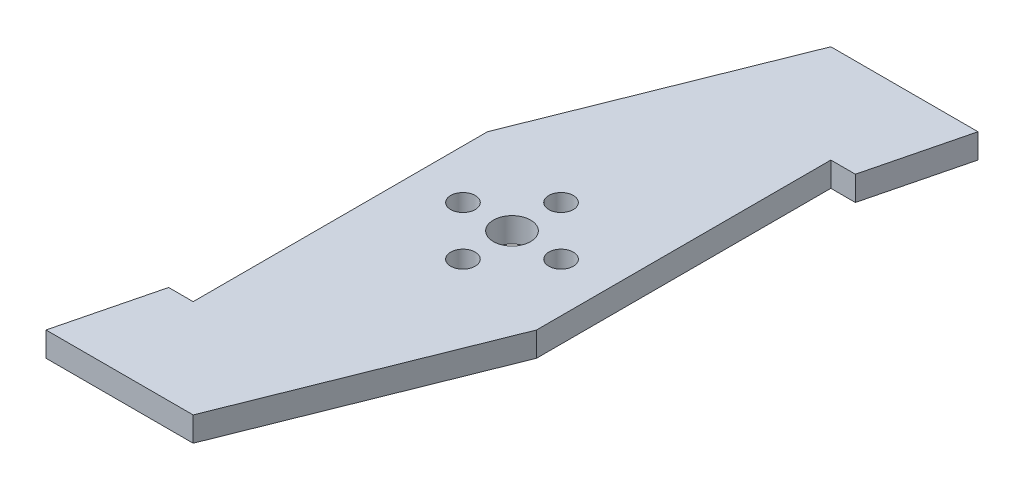
SolidWorks part; units mm, degrees
material "AISI Type A2 Tool Steel"
ref_plane "Front Plane" through (0, 0, 0) normal (0, 0, 1) x (1, 0, 0)
ref_plane "Top Plane" through (0, 0, 0) normal (0, 1, 0) x (1, 0, 0)
ref_plane "Right Plane" through (0, 0, 0) normal (1, 0, 0) x (0, 0, -1)
sketch "Sketch2" plane through (0, 0, 0) normal (0, 1, 0) x (1, 0, 0)
  line L14 (25.4, -82.55) -> (-25.4, -82.55)
  line L16 (25.4, -82.55) -> (25.4, 82.55)
  line L17 (-25.4, -82.55) -> (-25.4, 82.55)
  line L18 (25.4, 82.55) -> (-25.4, 82.55)
  line L19 (25.4, -82.55) -> (-25.4, 82.55) construction
  line L20 (-25.4, -82.55) -> (25.4, 82.55) construction
  circle A4 centre (0, 0) radius 82.55 construction
  arc A5 (-82.55, 0) -> (82.55, 0) centre (0, 0) cw
  dimension "D1" = 165.1
  dimension "D2" = 165.1
  dimension "D3" = 50.8
extrude "Boss-Extrude2" add sketch "Sketch2" along normal mid plane 6.35 contours A5 L17 L14 L16 | L18 L17 L14 L16 region at (0, 0, 0.6565)
sketch "Sketch6" plane through (0, 3.175, 0) normal (0, 1, 0) x (1, 0, 0)
  line L2 (31.75, 57.15) -> (25.4, 57.15)
  line L3 (25.4, 82.55) -> (25.4, 57.15)
  line L4 (-25.4, -82.55) -> (-38.1, -82.55)
  line L9 (-31.75, -57.15) -> (-38.1, -82.55)
  line L10 (-31.75, -57.15) -> (-25.4, -57.15)
  line L11 (-25.4, -82.55) -> (-25.4, -57.15)
  line L12 (25.4, -82.55) -> (-25.4, -82.55) construction
  line L13 (31.75, 57.15) -> (38.1, 82.55)
  line L15 (25.4, 82.55) -> (38.1, 82.55)
  point P10 (0, 0)
  point P13 (0, 0)
  point P14 (0, 0)
  dimension "D1" = 25.4
  dimension "D2" = 6.35
  dimension "D4" = 12.7
  dimension "D3" = 2
extrude "Boss-Extrude3" add sketch "Sketch6" against normal up to surface (6.35 mm away) contours L4 L9 L10 L11 | L15 L13 L2 L3 up to face at (0, -3.175, 0)
sketch "Sketch3" plane through (0, 3.175, 0) normal (0, 1, 0) x (1, 0, 0)
  circle A2 centre (0, 0) radius 4.826
  dimension "D1" = 9.652
extrude "Cut-Extrude1" cut sketch "Sketch3" against normal through all
sketch "Sketch4" plane through (0, 3.175, 0) normal (0, 1, 0) x (1, 0, 0)
  circle A0 centre (0, 12.7) radius 3.175
  circle A1 centre (-12.7, 0) radius 3.175
  circle A2 centre (0, -12.7) radius 3.175
  circle A3 centre (12.7, 0) radius 3.175
  point P11 (0, 0)
  dimension "D2" = 6.35
  dimension "D3" = 12.7
  dimension "D1" = 4
extrude "Cut-Extrude2" cut sketch "Sketch4" against normal through all
sketch "Sketch7" plane through (0, -3.175, 0) normal (0, -1, 0) x (-1, 0, 0)
  line L0 (0, 82.55) -> (25.4, 19.05)
  line L1 (-38.1, 82.55) -> (25.4, 82.55) construction
  line L3 (25.4, 19.05) -> (25.4, 82.55)
  line L4 (25.4, 82.55) -> (0, 82.55)
  line L5 (-38.1, 82.55) -> (38.1, -82.55) construction
  line L6 (25.4, 0) -> (-25.4, 0) construction
  line L7 (25.4, -57.15) -> (25.4, 82.55) construction
  line L8 (-25.4, -82.55) -> (-25.4, 57.15) construction
  line L11 (0, 82.55) -> (0, -82.55) construction
  line L12 (-25.4, -82.55) -> (38.1, -82.55) construction
  line L13 (0, -82.55) -> (-25.4, -19.05)
  line L14 (-25.4, -82.55) -> (0, -82.55)
  line L15 (-25.4, -19.05) -> (-25.4, -82.55)
  point P17 (0, 0)
  point P18 (0, 0)
  point P19 (-16.4946, -32.5367)
  point P25 (0, 0)
  dimension "D1" = 25.4
  dimension "D2" = 63.5
extrude "Cut-Extrude3" cut sketch "Sketch7" against normal through all
